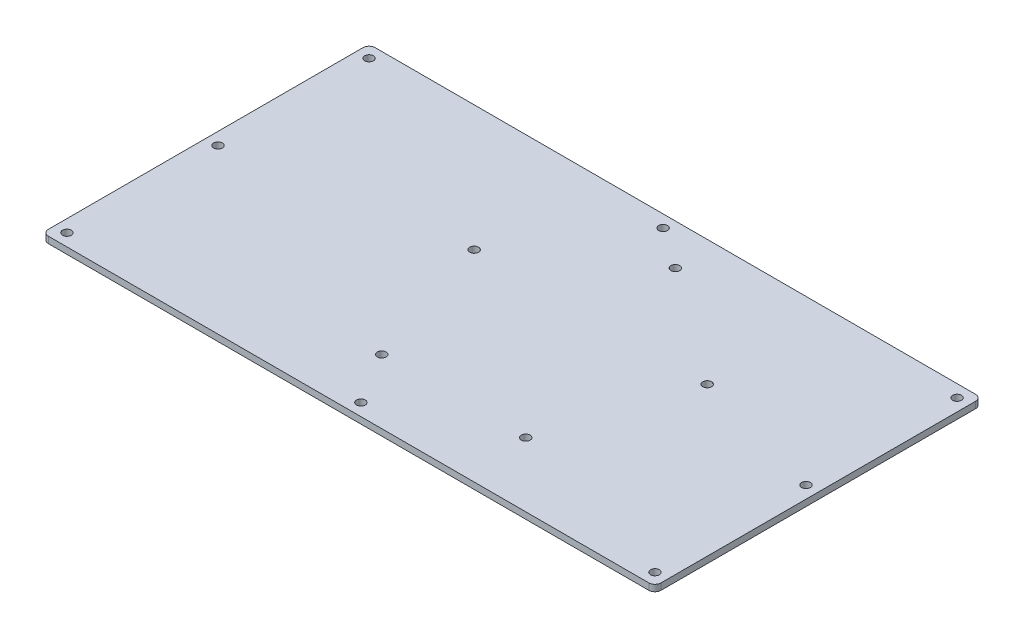
SolidWorks part; units mm, degrees
ref_plane "Front Plane" through (0, 0, 0) normal (0, 0, 1) x (1, 0, 0)
ref_plane "Top Plane" through (0, 0, 0) normal (0, 1, 0) x (1, 0, 0)
ref_plane "Right Plane" through (0, 0, 0) normal (1, 0, 0) x (0, 0, -1)
sketch "Sketch2" plane through (0, 0, 0) normal (0, 1, 0) x (1, 0, 0)
  line L0 (0, 80) -> (300, 80) construction
  line L1 (0, 0) -> (300, 0)
  line L2 (0, 0) -> (0, 160)
  line L3 (0, 160) -> (300, 160)
  line L4 (300, 0) -> (300, 160)
  line L5 (150, 160) -> (150, 0) construction
  line L6 (170, 160) -> (170, 0) construction
  circle A0 centre (170, 140) radius 2.15
  circle A1 centre (227.0634, 98.541) radius 2.15
  circle A2 centre (205.2671, 31.459) radius 2.15
  circle A3 centre (134.7329, 31.459) radius 2.15
  circle A4 centre (112.9366, 98.541) radius 2.15
  circle A5 centre (6, 6) radius 2.15
  circle A6 centre (294, 6) radius 2.15
  circle A7 centre (294, 154) radius 2.15
  circle A8 centre (6, 154) radius 2.15
  circle A9 centre (150, 6) radius 2.15
  circle A10 centre (6, 80) radius 2.15
  circle A11 centre (294, 80) radius 2.15
  circle A12 centre (150, 154) radius 2.15
  point P13 (170, 80)
  point P24 (170, 80)
  point P39 (170, 80)
  dimension "D4" = 4.3
  dimension "D7" = 4.3
  dimension "D10" = 4.3
  dimension "D12" = 4.3
  dimension "D1" = 300
  dimension "D2" = 160
  dimension "D3" = 170
  dimension "D5" = 60
  dimension "D8" = 6
  dimension "D9" = 6
  dimension "D11" = 6
  dimension "D13" = 6
  dimension "D6" = 5
extrude "Boss-Extrude2" add sketch "Sketch2" along normal blind 3.175
fillet "Fillet1" radius 3 4 edges at (0, 1.5875, 0) (300, 1.5875, 0) (300, 1.5875, -160) (0, 1.5875, -160)
